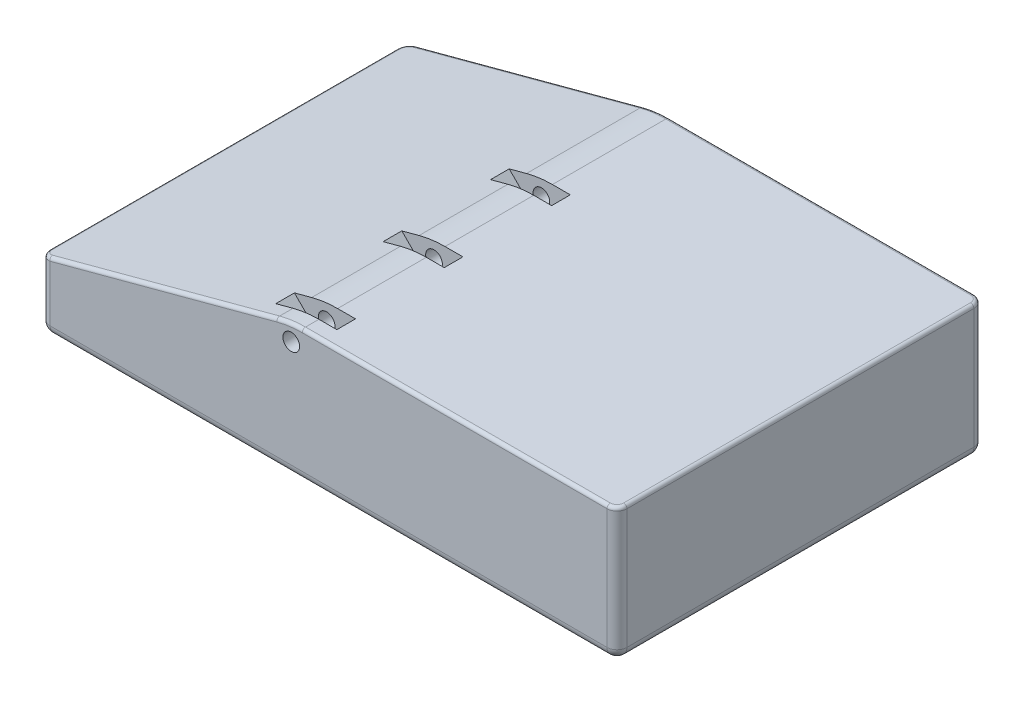
SolidWorks part; units mm, degrees
ref_plane "Front Plane" through (0, 0, 0) normal (0, 0, 1) x (1, 0, 0)
ref_plane "Top Plane" through (0, 0, 0) normal (0, 1, 0) x (1, 0, 0)
ref_plane "Right Plane" through (0, 0, 0) normal (1, 0, 0) x (0, 0, -1)
sketch "Sketch1" plane through (0, 0, 0) normal (0, 0, 1) x (1, 0, 0)
  line L0 (32.649, -10.2195) -> (26.049, -10.2195) construction
  line L1 (26.049, -10.2195) -> (26.049, -17.2195) construction
  line L2 (26.049, -17.2195) -> (-133.705, -17.2195) construction
  line L3 (-133.705, -17.2195) -> (-133.705, -10.2195) construction
  line L4 (-133.705, -10.2195) -> (-140.305, -10.2195) construction
  line L5 (-140.305, -10.2195) -> (-140.305, -17.2195) construction
  line L6 (-137.305, -20.2195) -> (29.649, -20.2195) construction
  line L7 (32.649, -17.2195) -> (32.649, -10.2195) construction
  line L8 (32.649, -10.2195) -> (32.649, 51.2443) construction
  line L9 (29.1601, 54.2042) -> (-74.6544, 37.0563) construction
  line L10 (-76.6042, 35.8436) -> (-80.3834, 30.5688) construction
  line L11 (-82.3332, 29.3562) -> (-137.7939, 20.1953) construction
  line L12 (-140.305, 17.2354) -> (-140.305, -10.2195) construction
  line L13 (-140.305, -10.2195) -> (-133.705, -10.2195) construction
  line L14 (-133.705, -10.2195) -> (-133.705, -0.2195) construction
  line L15 (-133.705, -0.2195) -> (-137.305, -0.2195) construction
  line L16 (-137.305, -0.2195) -> (-137.305, 17.2354) construction
  line L17 (-137.305, 17.2354) -> (-79.3922, 26.8013) construction
  line L18 (-79.3922, 26.8013) -> (-74.1655, 34.0964) construction
  line L19 (-74.1655, 34.0964) -> (29.649, 51.2443) construction
  line L20 (29.649, 51.2443) -> (29.649, -0.2195) construction
  line L21 (29.649, -0.2195) -> (26.049, -0.2195) construction
  line L22 (26.049, -0.2195) -> (26.049, -10.2195) construction
  line L23 (26.049, -10.2195) -> (32.649, -10.2195) construction
  line L24 (32.649, -10.2195) -> (26.049, -10.2195) construction
  line L25 (26.049, -10.2195) -> (26.049, -17.2195) construction
  line L26 (26.049, -17.2195) -> (-133.705, -17.2195) construction
  line L27 (-133.705, -17.2195) -> (-133.705, -10.2195) construction
  line L28 (-133.705, -10.2195) -> (-140.305, -10.2195) construction
  line L29 (-140.305, -10.2195) -> (-140.305, -17.2195) construction
  line L30 (-137.305, -20.2195) -> (29.649, -20.2195) construction
  line L31 (32.649, -17.2195) -> (32.649, -10.2195) construction
  line L32 (32.649, -10.2195) -> (32.649, 51.2443) construction
  line L33 (29.1601, 54.2042) -> (-74.6544, 37.0563) construction
  line L34 (-76.6042, 35.8436) -> (-80.3834, 30.5688) construction
  line L35 (-82.3332, 29.3562) -> (-137.7939, 20.1953) construction
  line L36 (-140.305, 17.2354) -> (-140.305, -10.2195) construction
  line L37 (-140.305, -10.2195) -> (-133.705, -10.2195) construction
  line L38 (-133.705, -10.2195) -> (-133.705, -0.2195) construction
  line L39 (-133.705, -0.2195) -> (-137.305, -0.2195) construction
  line L40 (-137.305, -0.2195) -> (-137.305, 17.2354) construction
  line L41 (-137.305, 17.2354) -> (-79.3922, 26.8013) construction
  line L42 (-79.3922, 26.8013) -> (-74.1655, 34.0964) construction
  line L43 (-74.1655, 34.0964) -> (29.649, 51.2443) construction
  line L44 (29.649, 51.2443) -> (29.649, -0.2195) construction
  line L45 (29.649, -0.2195) -> (26.049, -0.2195) construction
  line L46 (26.049, -0.2195) -> (26.049, -10.2195) construction
  line L47 (26.049, -10.2195) -> (32.649, -10.2195) construction
  line L48 (-140.305, -20.2195) -> (32.649, -20.2195)
  line L49 (32.649, -20.2195) -> (32.649, 19.7805)
  line L50 (32.649, 19.7805) -> (-65.664, 19.7805)
  line L51 (-65.664, 19.7805) -> (-140.305, -0.2195)
  line L52 (-140.305, -0.2195) -> (-140.305, -20.2195)
  line L53 (-140.305, -0.2195) -> (32.649, -0.2195) construction
  line L54 (32.649, 20.7805) -> (-65.0057, 20.7805) construction
  line L55 (-66.5586, 20.576) -> (-140.305, 0.8158) construction
  arc A0 (-140.305, -17.2195) -> (-137.305, -20.2195) centre (-137.305, -17.2195) ccw construction
  arc A1 (29.649, -20.2195) -> (32.649, -17.2195) centre (29.649, -17.2195) ccw construction
  arc A2 (32.649, 51.2443) -> (29.1601, 54.2042) centre (29.649, 51.2443) ccw construction
  arc A3 (-74.6544, 37.0563) -> (-76.6042, 35.8436) centre (-74.1655, 34.0964) ccw construction
  arc A4 (-82.3332, 29.3562) -> (-80.3834, 30.5688) centre (-82.8221, 32.3161) ccw construction
  arc A5 (-137.7939, 20.1953) -> (-140.305, 17.2354) centre (-137.305, 17.2354) ccw construction
  arc A6 (-140.305, -17.2195) -> (-137.305, -20.2195) centre (-137.305, -17.2195) ccw construction
  arc A7 (29.649, -20.2195) -> (32.649, -17.2195) centre (29.649, -17.2195) ccw construction
  arc A8 (32.649, 51.2443) -> (29.1601, 54.2042) centre (29.649, 51.2443) ccw construction
  arc A9 (-74.6544, 37.0563) -> (-76.6042, 35.8436) centre (-74.1655, 34.0964) ccw construction
  arc A10 (-82.3332, 29.3562) -> (-80.3834, 30.5688) centre (-82.8221, 32.3161) ccw construction
  arc A11 (-137.7939, 20.1953) -> (-140.305, 17.2354) centre (-137.305, 17.2354) ccw construction
  arc A12 (-65.0057, 20.7805) -> (-66.5586, 20.576) centre (-65.0057, 14.7805) ccw construction
  circle A13 centre (-65.0057, 14.7805) radius 5 construction
  point P27 (0, 0)
  dimension "D5" = 10
  dimension "D1" = 20
  dimension "D2" = 40
  dimension "D3" = 15
  dimension "D4" = 2
extrude "Boss-Extrude1" add sketch "Sketch1" along normal blind 110
shell "Shell1" thickness 5 removed face at (-53.828, -20.2195, 55)
sketch "Sketch3" plane through (0, 0, 0) normal (0, 0, -1) x (-1, 0, 0)
  line L0 (-32.649, 19.7805) -> (65.664, 19.7805) construction
  line L1 (65.664, 19.7805) -> (140.305, -0.2195) construction
  line L3 (60.6756, 12.2805) -> (56.3455, 19.7805)
  line L4 (68.5413, 11.245) -> (74.665, 17.3687)
  line L5 (74.665, 17.3687) -> (65.664, 19.7805)
  line L6 (65.664, 19.7805) -> (56.3455, 19.7805)
  line L7 (69.8354, 13.4864) -> (71.1294, 18.316) construction
  circle A0 centre (65.0057, 14.7805) radius 2.5
  arc A1 (60.6756, 12.2805) -> (68.5413, 11.245) centre (65.0057, 14.7805) ccw
  circle A4 centre (65.0057, 14.7805) radius 5 construction
  line M13 (140.305, -0.2195) -> (65.664, 19.7805)
  line M14 (65.664, 19.7805) -> (-32.649, 19.7805)
  dimension "D1" = 5
  dimension "D2" = 10
  dimension "D3" = 30
extrude "Boss-Extrude2" add sketch "Sketch3" against normal up to next contours L3 A1 L4 A0 M13 M14 region at (-58.6913, 16.1348, 0)
extrude "Cut-Extrude8" cut sketch "Sketch3<4>" against normal blind 5.6 from offset 35 contours L3 A1 L4 A0 M13 M14 | A0 region at (-58.6913, 16.1348, 0) region at (-65.0057, 14.7805, 0) offset against normal yes
sketch "Sketch3<4>" plane through (0, 0, 0) normal (0, 0, -1) x (-1, 0, 0) same geometry as "Sketch3"
extrude "Cut-Extrude9" cut sketch "Sketch3<5>" against normal through all contours A0 region at (-65.0057, 14.7805, 0)
sketch "Sketch3<5>" plane through (0, 0, 0) normal (0, 0, -1) x (-1, 0, 0) same geometry as "Sketch3"
pattern_linear "LPattern1" count 3 spacing 32.2 along (0, 0, 1) of "Cut-Extrude8"
fillet "Fillet1" radius 3 8 edges at (-140.305, -10.2195, 110) (-140.305, -20.2195, 55) (-140.305, -10.2195, 0) (32.649, -20.2195, 55) (-53.828, -20.2195, 110) (-53.828, -20.2195, 0) (32.649, -0.2195, 0) (32.649, -0.2195, 110)
fillet "Fillet2" radius 1 10 edges at (-101.4845, 10.1824, 110) (-139.4263, 0.0159, 109.1213) (-140.305, -0.2195, 55) (-139.4263, 0.0159, 0.8787) (-18.0075, 19.7805, 110) (31.7703, 19.7805, 109.1213) (32.649, 19.7805, 55) (31.7703, 19.7805, 0.8787) (-101.4845, 10.1824, 0) (-18.0075, 19.7805, 0)
fillet "Fillet3" radius 30 6 edges at (-65.6254, 19.4876, 0.2929) (-65.6254, 19.4876, 109.7071) (-65.664, 19.7805, 107) (-65.664, 19.7805, 86.1) (-65.664, 19.7805, 53.9) (-65.664, 19.7805, 18)
